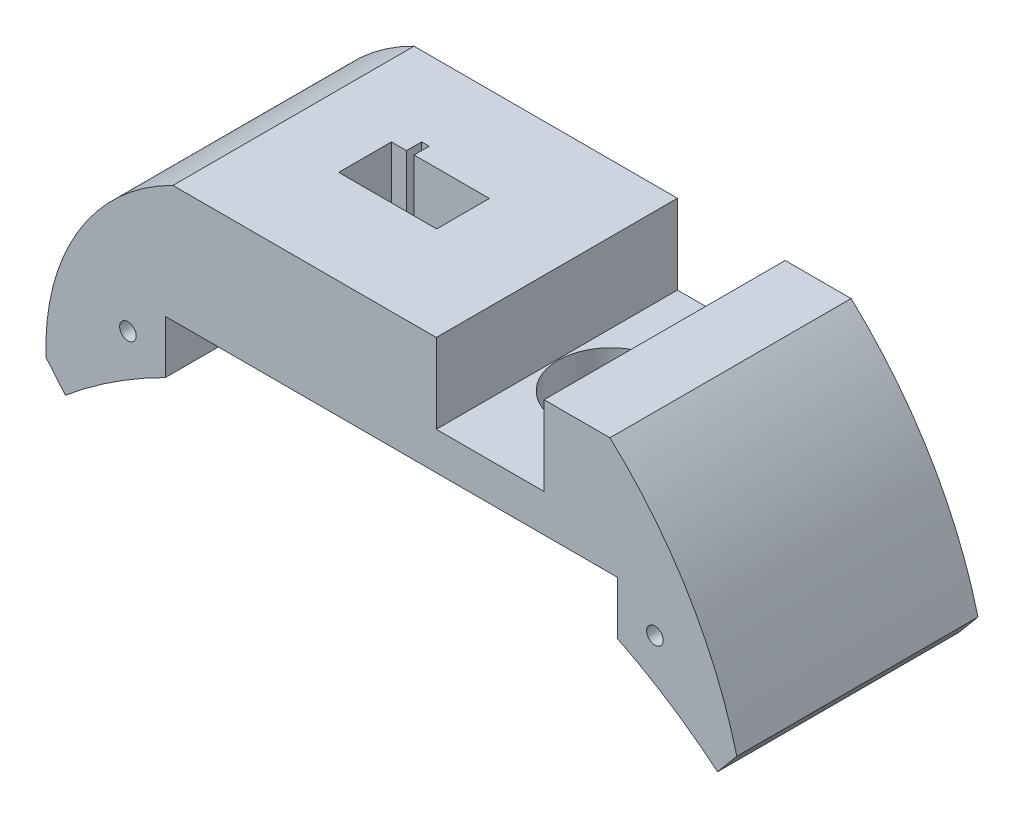
SolidWorks part; units mm, degrees
ref_plane "Płaszczyzna przednia" through (0, 0, 0) normal (0, 0, 1) x (1, 0, 0)
ref_plane "Płaszczyzna górna" through (0, 0, 0) normal (0, 1, 0) x (1, 0, 0)
ref_plane "Płaszczyzna prawa" through (0, 0, 0) normal (1, 0, 0) x (0, 0, -1)
sketch "Szkic2" plane through (0, 0, 0) normal (0, 0, 1) x (1, 0, 0)
  line L0 (2256.522, 726.2547) -> (2253.9561, 729.3232)
  line L1 (2343.0615, 726.2547) -> (2345.6274, 729.3232)
  line L2 (2328.7917, 757.508) -> (2270.7917, 757.508)
  line L3 (2299.7917, 741.9616) -> (2269.7917, 741.9616)
  line L4 (2299.7917, 741.9616) -> (2329.7917, 741.9616)
  line L5 (2269.7917, 741.9616) -> (2269.7917, 734.9232)
  line L6 (2329.7917, 741.9616) -> (2329.7917, 734.9232)
  arc A0 (2253.9561, 729.3232) -> (2270.7917, 757.508) centre (2284.0743, 730.4533) cw
  arc A1 (2256.522, 726.2547) -> (2343.0615, 726.2547) centre (2299.7917, 674.508) cw construction
  arc A2 (2345.6274, 729.3232) -> (2328.7917, 757.508) centre (2289.6344, 714.9975) ccw
  arc A3 (2256.522, 726.2547) -> (2269.7917, 734.9232) centre (2299.7917, 674.508) cw
  arc A4 (2343.0615, 726.2547) -> (2329.7917, 734.9232) centre (2299.7917, 674.508) ccw
  point P7 (2256.522, 726.2547)
  point P8 (2343.0615, 726.2547)
  dimension "D3" = 30
  dimension "D1" = 4
  dimension "D4" = 4
  dimension "D5" = 83
  dimension "D6" = 58
  dimension "D7" = 29
  dimension "D8" = 30
extrude "Dodanie-wyciągnięcie1" add sketch "Szkic2" along normal blind 32
sketch "Szkic3" plane through (0, 741.9616, 0) normal (0, -1, 0) x (1, 0, 0)
  circle A0 centre (2312.8917, 16) radius 7
extrude "Wytnij-wyciągnięcie1" cut sketch "Szkic3" against normal through all
sketch "Szkic4" plane through (0, 757.508, 0) normal (0, 1, 0) x (1, 0, 0)
  line L0 (2328.7917, 0) -> (2270.7917, 0) construction
  line L1 (2305.7417, 0) -> (2320.0417, 0)
  line L2 (2305.7417, 0) -> (2305.7417, -32)
  line L3 (2305.7417, -32) -> (2320.0417, -32)
  line L4 (2320.0417, 0) -> (2320.0417, -32)
  line L5 (2328.7917, -32) -> (2270.7917, -32) construction
  line L6 (2305.9917, -28.75) -> (2305.9917, -3.25) construction
  line L7 (2319.7917, -3.25) -> (2319.7917, -28.75) construction
  dimension "D1" = 0.25
  dimension "D2" = 0.25
extrude "Wytnij-wyciągnięcie2" cut sketch "Szkic4" against normal blind 10.55
sketch "Szkic5" plane through (0, 0, 0) normal (0, 0, -1) x (-1, 0, 0)
  circle A0 centre (-2264.8227, 737.7613) radius 1.1
  circle A1 centre (-2334.7607, 737.7613) radius 1.1
sketch "Szkic7" plane through (0, 741.9616, 0) normal (0, -1, 0) x (1, 0, 0)
  line L0 (2269.7917, 32) -> (2269.7917, 0) construction
  line L1 (2280.2917, 19.5) -> (2293.2917, 19.5)
  line L2 (2280.2917, 19.5) -> (2280.2917, 12.5)
  line L4 (2293.2917, 19.5) -> (2293.2917, 12.5)
  line L5 (2269.7917, 32) -> (2329.7917, 32) construction
  line L6 (2282.2917, 12.5) -> (2282.2917, 10.5)
  line L7 (2282.2917, 10.5) -> (2283.2917, 10.5)
  line L8 (2283.2917, 10.5) -> (2283.2917, 12.5)
  line L9 (2283.2917, 12.5) -> (2293.2917, 12.5)
  line L10 (2282.2917, 12.5) -> (2280.2917, 12.5)
  dimension "D1" = 13
  dimension "D2" = 10.5
  dimension "D3" = 7
  dimension "D4" = 12.5
  dimension "D5" = 1
  dimension "D6" = 2
  dimension "D7" = 2
  dimension "D8" = 7
extrude "Wytnij-wyciągnięcie3" cut sketch "Szkic7" against normal through all
extrude "Wytnij-wyciągnięcie4" cut sketch "Szkic5" against normal through all
